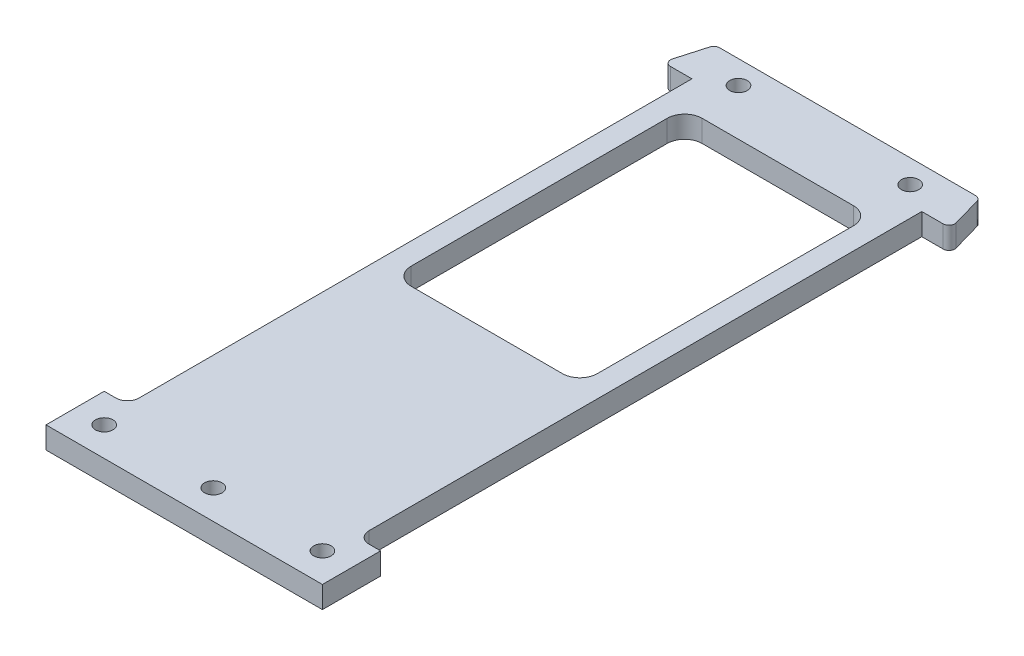
SolidWorks part; units mm, degrees
material "1060 Alloy"
ref_plane "Front Plane" through (0, 0, 0) normal (0, 0, 1) x (1, 0, 0)
ref_plane "Top Plane" through (0, 0, 0) normal (0, 1, 0) x (1, 0, 0)
ref_plane "Right Plane" through (0, 0, 0) normal (1, 0, 0) x (0, 0, -1)
sketch "Sketch1" plane through (0, 0, 0) normal (0, 1, 0) x (1, 0, 0)
  line L0 (0, 10) -> (4, 10)
  line L1 (0, 0) -> (47.5, 0)
  line L2 (0, 0) -> (0, 10)
  line L3 (4, 114) -> (43.5, 114)
  line L4 (47.5, 0) -> (47.5, 10)
  line L5 (7.75, 102) -> (39.75, 102)
  line L6 (7.75, 102) -> (7.75, 52)
  line L7 (7.75, 52) -> (39.75, 52)
  line L8 (39.75, 102) -> (39.75, 52)
  line L9 (43.5, 114) -> (43.5, 10)
  line L10 (43.5, 10) -> (47.5, 10)
  line L11 (4, 114) -> (4, 10)
  line L12 (23.75, 5) -> (23.75, 0) construction
  circle A0 centre (5, 5) radius 1.5
  circle A1 centre (42.5, 5) radius 1.5
  circle A2 centre (23.75, 5) radius 1.5
  circle A3 centre (9, 110) radius 1.5
  circle A4 centre (38.5, 110) radius 1.5
  dimension "D7" = 3
  dimension "D12" = 3
  dimension "D1" = 47.5
  dimension "D2" = 32
  dimension "D3" = 50
  dimension "D4" = 3.75
  dimension "D5" = 12
  dimension "D6" = 52
  dimension "D8" = 5
  dimension "D9" = 5
  dimension "D10" = 5
  dimension "D13" = 10
  dimension "D14" = 3.75
  dimension "D15" = 4
  dimension "D16" = 5
  dimension "D17" = 5
extrude "Boss-Extrude1" add sketch "Sketch1" along normal blind 3.75
fillet "Fillet1" radius 3 4 edges at (39.75, 1.875, -52) (7.75, 1.875, -52) (39.75, 1.875, -102) (7.75, 1.875, -102)
sketch "Sketch2" plane through (0, 3.75, 0) normal (0, 1, 0) x (1, 0, 0)
  line L0 (4, 114) -> (1, 114)
  line L1 (1, 114) -> (-1, 107)
  line L2 (-1, 107) -> (4, 107)
  line L4 (4, 107) -> (4, 114)
  line L5 (43.5, 114) -> (46.5, 114)
  line L6 (46.5, 114) -> (48.5, 107)
  line L7 (48.5, 107) -> (43.5, 107)
  line L9 (43.5, 107) -> (43.5, 114)
  line L10 (43.5, 114) -> (4, 114) construction
  line L11 (4, 114) -> (4, 10) construction
  dimension "D1" = 7
  dimension "D2" = 5
  dimension "D3" = 3
extrude "Boss-Extrude2" add sketch "Sketch2" against normal up to surface (3.75 mm away) up to face at (9, 0, -108.5)
fillet "Fillet2" radius 1 4 edges at (46.5, 1.875, -114) (48.5, 1.875, -107) (-1, 1.875, -107) (1, 1.875, -114)
fillet "Fillet3" radius 2 2 edges at (4, 1.875, -10) (43.5, 1.875, -10)
